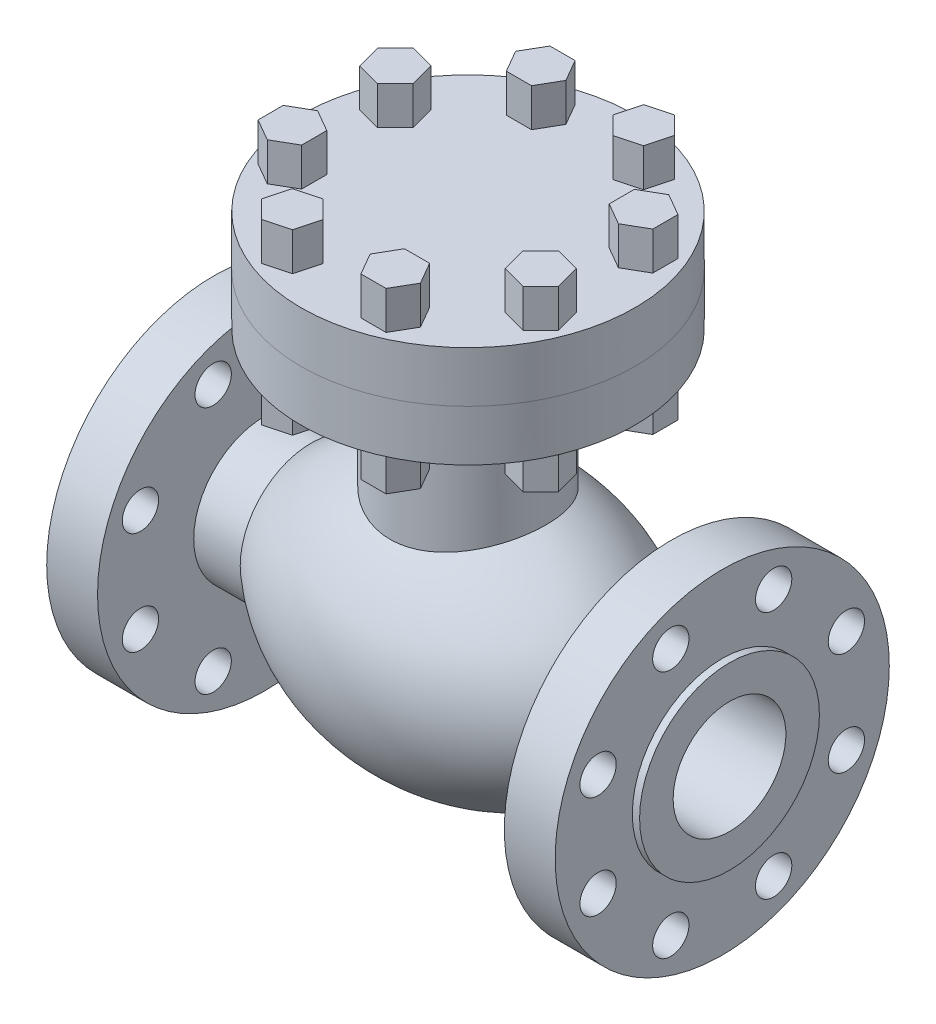
SolidWorks part; units mm, degrees
ref_plane "Front Plane" through (0, 0, 0) normal (0, 0, 1) x (1, 0, 0)
ref_plane "Top Plane" through (0, 0, 0) normal (0, 1, 0) x (1, 0, 0)
ref_plane "Right Plane" through (0, 0, 0) normal (1, 0, 0) x (0, 0, -1)
sketch "Flow Extrude Sketch" plane through (0, 0, 0) normal (0, 0, 1) x (1, 0, 0)
  line L0 (-245.3211, 0) -> (194.8025, 0) construction
  line L1 (0, 0) -> (0, 85.3189) construction
  line L2 (137.16, 61.976) -> (228.6, 61.976)
  line L3 (-228.6, 61.976) -> (-137.16, 61.976)
  line L4 (-228.6, 61.976) -> (-228.6, 0)
  line L5 (-228.6, 0) -> (228.6, 0)
  line L6 (228.6, 61.976) -> (228.6, 0)
  arc A1 (-137.16, 61.976) -> (137.16, 61.976) centre (0, -91.6348) cw
  point P13 (0, 114.3)
  dimension "A" = 457.2
  dimension "A*.6" = 274.32
  dimension "d+2*t" = 123.952
  dimension "A*.5" = 228.6
revolve "Flow Extrude" add sketch "Flow Extrude Sketch" angle 360 about L0
sketch "Flow Flange Sketch" plane through (228.6, 0, 0) normal (1, 0, 0) x (0, 0, -1)
  circle A0 centre (0, 0) radius 146.05
  dimension "O" = 292.1
extrude "Flow Flange" add sketch "Flow Flange Sketch" against normal blind 50.8
sketch "Hub Cut Sketch" plane through (228.6, 0, 0) normal (1, 0, 0) x (0, 0, -1)
  circle A0 centre (0, 0) radius 78.613
  dimension "R" = 157.226
extrude "Hub Cut" cut sketch "Hub Cut Sketch" against normal blind 6.35 flip side to cut
sketch "Bolt Hole Sketch" plane through (228.6, 0, 0) normal (1, 0, 0) x (0, 0, -1)
  line L0 (0, 0) -> (0, 106.0153) construction
  line L1 (0, 0) -> (42.3389, 102.215) construction
  circle A0 centre (0, 0) radius 117.475 construction
  circle A1 centre (44.9557, 108.5327) radius 15.875
  dimension "BC" = 234.95
  dimension "DH" = 31.75
  dimension "Angle" = 22.5
extrude "Bolt Hole" cut sketch "Bolt Hole Sketch" against normal up to next
pattern_circular "Bolt Hole Pattern" count 8 every 45 about axis through (-245.3211, 0, 0) along (1, 0, 0) of "Bolt Hole"
mirror "Flange Mirror" about plane through (0, 0, 0) normal (1, 0, 0) of "Bolt Hole Pattern", "Bolt Hole", "Hub Cut", "Flow Flange"
sketch "Body Extrude Sketch" plane through (0, 0, 0) normal (0, 1, 0) x (1, 0, 0)
  line L1 (0, -96.6135) -> (0, 96.6135) construction
  circle A0 centre (0, 0) radius 68.1736
  dimension "(d+2* t)*1.05" = 136.3472
extrude "Body Extrude" add sketch "Body Extrude Sketch" along normal blind 306.07
sketch "Flange Bottom Sketch" plane through (0, 306.07, 0) normal (0, 1, 0) x (-1, 0, 0)
  circle A0 centre (0, 0) radius 146.05
  dimension "O" = 292.1
extrude "Flange Bottom" add sketch "Flange Bottom Sketch" against normal blind 44.45
sketch "Flange Top Sketch" plane through (0, 261.62, 0) normal (0, -1, 0) x (1, 0, 0)
  circle A1 centre (0, 0) radius 146.05
  circle A2 centre (0, 0) radius 146.05
  dimension "D1" = 0
extrude "Flange Top" add sketch "Flange Top Sketch" along normal blind 44.45
sketch "ID Sketch" plane through (228.6, 0, 0) normal (-1, 0, 0) x (0, 0, 1)
  circle A0 centre (0, 0) radius 49.276
  dimension "d" = 98.552
extrude "ID Cut" cut sketch "ID Sketch" along normal through all
ref_plane "Bolt Plane" through (0, 339.4075, 0) normal (0, 1, 0) x (-1, 0, 0)
sketch "Bolt Sketch" plane through (0, 339.4075, 0) normal (0, 1, 0) x (-1, 0, 0)
  line L0 (0, 0) -> (-127.3205, -52.7379) construction
  line L1 (0, 0) -> (-142.2485, 0) construction
  line L2 (-108.5327, -22.9587) -> (-127.5827, -33.9572)
  line L3 (-127.5827, -33.9572) -> (-127.5827, -55.9543)
  line L4 (-127.5827, -55.9543) -> (-108.5327, -66.9528)
  line L5 (-108.5327, -66.9528) -> (-89.4827, -55.9543)
  line L6 (-89.4827, -55.9543) -> (-89.4827, -33.9572)
  line L7 (-89.4827, -33.9572) -> (-108.5327, -22.9587)
  circle A0 centre (0, 0) radius 117.475 construction
  circle A2 centre (-108.5327, -44.9557) radius 19.05 construction
  dimension "BC" = 234.95
  dimension "DH*1.2" = 38.1
  dimension "Angle" = 22.5
extrude "Bolt" add sketch "Bolt Sketch" against normal blind 155.575
pattern_circular "Bolt Pattern" count 8 every 45 about axis through (0, 261.62, 0) along (0, 1, 0) of "Bolt"
sketch "Sketch1" plane through (0, 0, 0) normal (0, 0, 1) x (1, 0, 0)
  line L1 (-146.05, 261.62) -> (146.05, 261.62)
  line L2 (-146.05, 261.62) -> (146.05, 261.62)
  dimension "D1" = 0
split line "Split Line1"
sketch "CPointSketch" plane through (0, 0, 0) normal (0, 0, 1) x (1, 0, 0)
  line L2 (228.6, -61.976) -> (228.6, 61.976) construction
  line L3 (-228.6, 61.976) -> (-228.6, -61.976) construction
  point P0 (-228.6, 0)
  point P1 (228.6, 0)
  point P4 (0, 0)
other "CPoint1" parameters "Diameter"=101.6, "StubLength"=0
ref_axis "Axis1" through (238.6, 0, 0) along (-1, 0, 0)
other "CPoint2" parameters "Diameter"=101.6, "StubLength"=0
ref_axis "Axis2" through (-238.6, 0, 0) along (1, 0, 0)
other "RPoint1"
